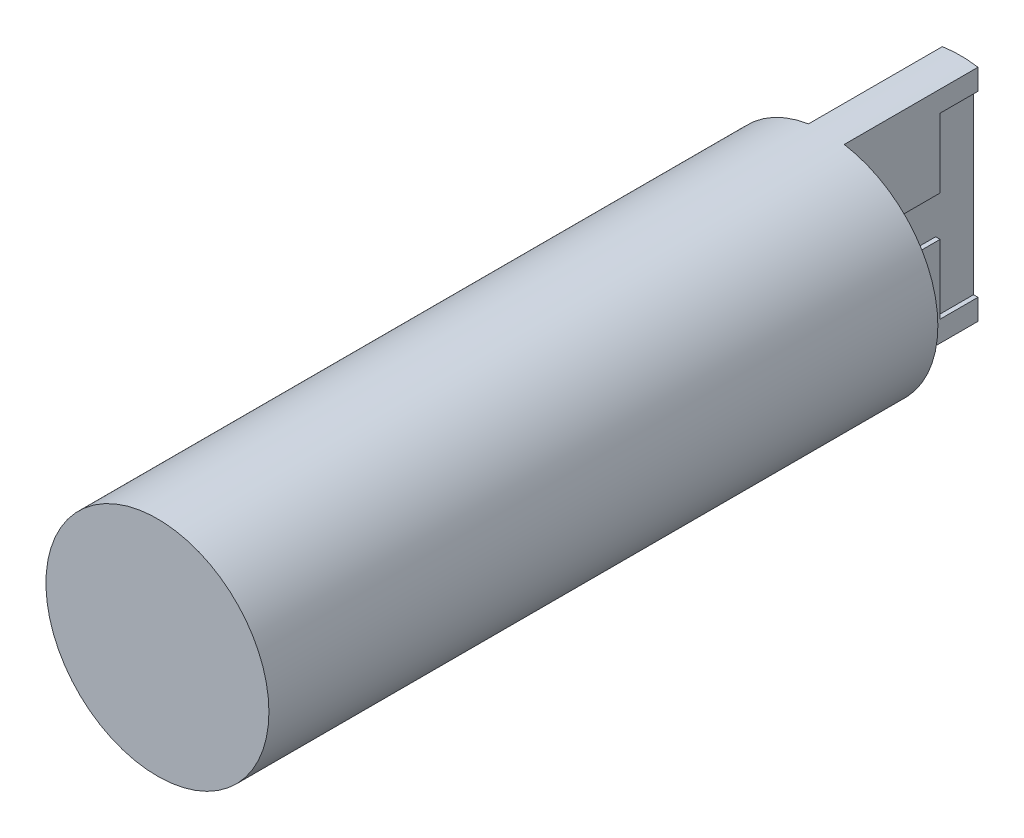
SolidWorks part; units mm, degrees
ref_plane "Plan de face" through (0, 0, 0) normal (0, 0, 1) x (1, 0, 0)
ref_plane "Plan de dessus" through (0, 0, 0) normal (0, 1, 0) x (1, 0, 0)
ref_plane "Plan de droite" through (0, 0, 0) normal (1, 0, 0) x (0, 0, -1)
sketch "Esquisse1" plane through (0, 0, 0) normal (0, 0, 1) x (1, 0, 0)
  circle A0 centre (0, 0) radius 25
  dimension "D1" = 50
extrude "Boss.-Extru.1" add sketch "Esquisse1" along normal blind 150
sketch "Esquisse2" plane through (0, 0, 0) normal (0, 0, -1) x (-1, 0, 0)
  line L0 (0, 0) -> (0, 38.1422) construction
  line L1 (0, 0) -> (59.9191, 0) construction
  line L4 (-4, -24.6779) -> (-4, 24.6779)
  line L6 (4, -24.6779) -> (4, 24.6779)
  line L7 (-4, -24.6779) -> (4, 24.6779) construction
  line L8 (-4, 24.6779) -> (4, -24.6779) construction
  circle A0 centre (0, 0) radius 25 construction
  arc A1 (4, 24.6779) -> (-4, 24.6779) centre (0, 0) ccw
  arc A2 (-4, -24.6779) -> (4, -24.6779) centre (0, 0) ccw
  dimension "D1" = 8
extrude "Boss.-Extru.2" add sketch "Esquisse2" along normal blind 30
sketch "Esquisse3" plane through (-4, 0, 0) normal (-1, 0, 0) x (0, 0, 1)
  line L0 (0, 0) -> (-30, 0) construction
  line L1 (0, -24.6779) -> (0, 24.6779) construction
  line L2 (-30, -24.6779) -> (-30, 24.6779) construction
  circle A0 centre (-26, 0) radius 4
  dimension "D1" = 8
extrude "Boss.-Extru.3" add sketch "Esquisse3" along normal blind 9 draft 1 contours A0
sketch "Esquisse4" plane through (4, 0, 0) normal (1, 0, 0) x (0, 0, -1)
  line L0 (0, 0) -> (30, 0) construction
  line L1 (0, 24.6779) -> (0, -24.6779) construction
  line L2 (30, 24.6779) -> (30, -24.6779) construction
  line L3 (21.5, 4.5) -> (21.5, 20)
  line L4 (6, 4.5) -> (21.5, 4.5)
  line L5 (6, 4.5) -> (6, -4.5)
  line L6 (6, -4.5) -> (21.5, -4.5)
  line L8 (6, 4.5) -> (26, -4.5) construction
  line L9 (6, -4.5) -> (26, 4.5) construction
  line L10 (30.5, -20) -> (21.5, -20)
  line L11 (30.5, -20) -> (30.5, -4.5)
  line L12 (30.5, 20) -> (21.5, 20)
  line L13 (21.5, -20) -> (21.5, -4.5)
  line L14 (30.5, -20) -> (21.5, 20) construction
  line L15 (30.5, 20) -> (21.5, -20) construction
  line L16 (30.5, -4.5) -> (30, -4.5)
  line L17 (30.5, 4.5) -> (30, 4.5)
  line L20 (30, 4.5) -> (30, -4.5)
  line L21 (30.5, 4.5) -> (30.5, 20)
  circle A0 centre (26, 0) radius 4 construction
  circle A1 centre (26, 0) radius 4 construction
  circle A2 centre (26, 0) radius 4.5 construction
  point P10 (16, 0)
  dimension "D1" = 9
  dimension "D3" = 40
extrude "Enlèv. mat.-Extru.1" cut sketch "Esquisse4" against normal blind 1
ref_axis "Axe1" through (0, 0, -39) along (0, 0, 1)
